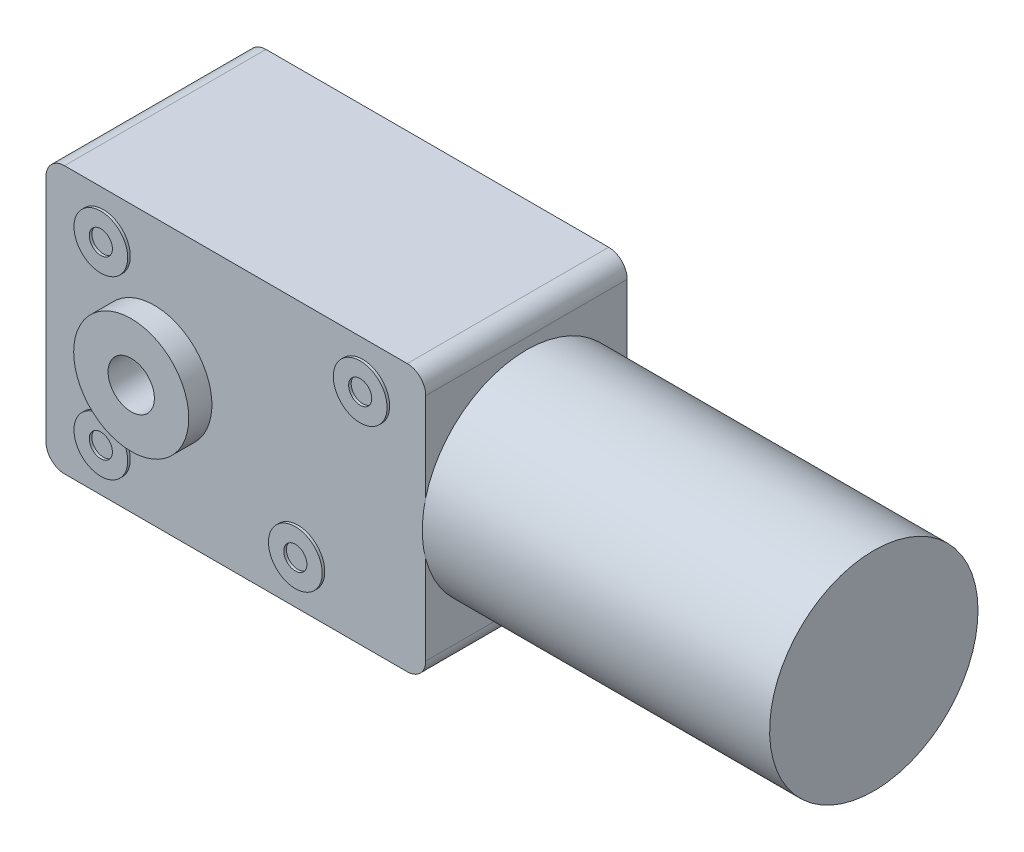
SolidWorks part; units mm, degrees
ref_plane "정면" through (0, 0, 0) normal (0, 0, 1) x (1, 0, 0)
ref_plane "윗면" through (0, 0, 0) normal (0, 1, 0) x (1, 0, 0)
ref_plane "우측면" through (0, 0, 0) normal (1, 0, 0) x (0, 0, -1)
sketch "스케치2" plane through (0, 0, 0) normal (0, 0, 1) x (1, 0, 0)
  line L1 (-37, 28.82) -> (37, 28.82)
  line L2 (-41, 24.82) -> (-41, -24.82)
  line L3 (-37, -28.82) -> (37, -28.82)
  line L4 (41, 24.82) -> (41, -24.82)
  line L5 (-41, 28.82) -> (41, -28.82) construction
  line L6 (-41, -28.82) -> (41, 28.82) construction
  arc A0 (37, 28.82) -> (41, 24.82) centre (37, 24.82) cw
  arc A1 (37, -28.82) -> (41, -24.82) centre (37, -24.82) ccw
  arc A2 (-41, -24.82) -> (-37, -28.82) centre (-37, -24.82) ccw
  arc A3 (-37, 28.82) -> (-41, 24.82) centre (-37, 24.82) ccw
  point P0 (0, 0)
  dimension "D3" = 4
  dimension "D1" = 57.64
  dimension "D2" = 82
extrude "보스-돌출1" add sketch "스케치2" along normal blind 43.5
sketch "스케치3" plane through (0, 0, 43.5) normal (0, 0, 1) x (1, 0, 0)
  line L0 (-41, 24.82) -> (-41, -24.82) construction
  line L1 (37, 28.82) -> (-37, 28.82) construction
  circle A0 centre (-17.6, 0) radius 12.42
  circle A1 centre (-17.6, 0) radius 5
  circle A2 centre (-28.6, 19) radius 5.8
  circle A3 centre (-28.6, -19) radius 5.8
  circle A4 centre (27.4, 19) radius 5.8
  circle A5 centre (13.4, -19) radius 5.8
  circle A6 centre (-28.6, 19) radius 2.5
  circle A7 centre (27.4, 19) radius 2.5
  circle A8 centre (13.4, -19) radius 2.5
  circle A9 centre (-28.6, -19) radius 2.5
  dimension "D1" = 11.6
  dimension "D3" = 11.6
  dimension "D4" = 11.6
  dimension "D6" = 11.6
  dimension "D12" = 10
  dimension "D13" = 24.84
  dimension "D14" = 5
  dimension "D15" = 5
  dimension "D16" = 5
  dimension "D17" = 5
  dimension "D2" = 56
  dimension "D5" = 12.4
  dimension "D7" = 42
  dimension "D8" = 38
  dimension "D9" = 9.82
  dimension "D10" = 23.4
  dimension "D11" = 28.82
extrude "보스-돌출2" add sketch "스케치3" along normal blind 0.5575 contours A2 A6 | A3 A9 | A5 A8 | A4 A7 region at (-34.236, 19, 43.5) region at (-34.236, -19, 43.5) region at (21.764, 19, 43.5) region at (7.764, -19, 43.5)
extrude "보스-돌출3" add sketch "스케치3<3>" along normal blind 5 contours A0 A1 region at (-29.6687, 0, 43.5)
sketch "스케치3<3>" plane through (0, 0, 43.5) normal (0, 0, 1) x (1, 0, 0) same geometry as "스케치3"
sketch "스케치4" plane through (41, 0, 0) normal (1, 0, 0) x (0, 0, -1)
  line L0 (0, -24.82) -> (0, 24.82) construction
  circle A0 centre (-21.75, 0) radius 22.5
  dimension "D1" = 45
  dimension "D2" = 21.75
extrude "보스-돌출4" add sketch "스케치4" along normal blind 75
extrude "컷-돌출1" cut sketch "스케치3<4>" against normal blind 10 contours A1 region at (-17.6, 0, 43.5)
sketch "스케치3<4>" plane through (0, 0, 43.5) normal (0, 0, 1) x (1, 0, 0) same geometry as "스케치3"
